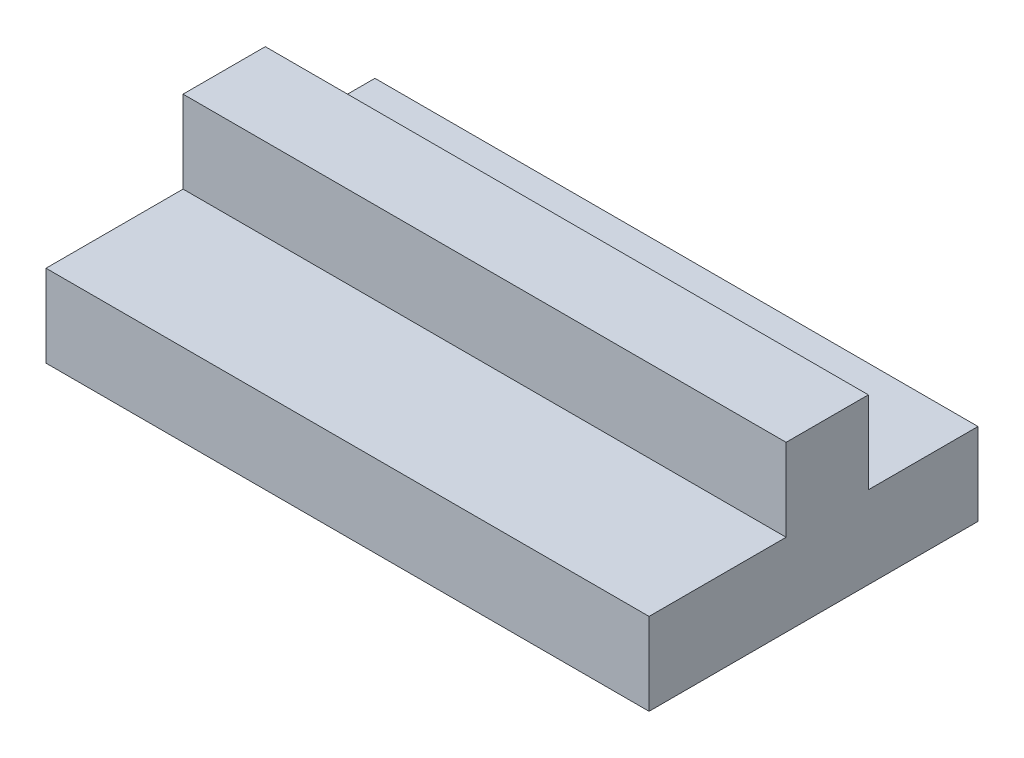
SolidWorks part; units mm, degrees
material "PET"
ref_plane "Спереди" through (0, 0, 0) normal (0, 0, 1) x (1, 0, 0)
ref_plane "Сверху" through (0, 0, 0) normal (0, 1, 0) x (1, 0, 0)
ref_plane "Справа" through (0, 0, 0) normal (1, 0, 0) x (0, 0, -1)
other "Configuration Table"
sketch "Основание & крышка" plane through (0, 0, 0) normal (0, 1, 0) x (1, 0, 0)
  line L1 (105, -26.5) -> (-105, -26.5)
  line L2 (105, -26.5) -> (105, 26.5)
  line L3 (105, 26.5) -> (-105, 26.5)
  line L4 (-105, -26.5) -> (-105, 26.5)
  line L5 (105, -26.5) -> (-105, 26.5) construction
  line L6 (105, 26.5) -> (-105, -26.5) construction
  line L7 (100, -21.5) -> (-100, -21.5)
  line L8 (100, -21.5) -> (100, 21.5)
  line L9 (100, 21.5) -> (-100, 21.5)
  line L10 (-100, -21.5) -> (-100, 21.5)
  line L11 (100, -21.5) -> (-100, 21.5) construction
  line L12 (100, 21.5) -> (-100, -21.5) construction
  point P0 (0, 0)
  point P5 (0, 0)
  dimension "D1" = 210
  dimension "D2" = 53
  dimension "D3" = 43
  dimension "D4" = 200
extrude "Бобышка-Вытянуть1" add sketch "Основание & крышка" along normal blind 50 contours L3 L4 L1 L2
sketch "Эскиз3" plane through (0, 0, 0) normal (0, -1, 0) x (1, 0, 0)
  line L0 (105, 26.5) -> (-105, 26.5) construction
  line L1 (-100, -21.5) -> (100, -21.5)
  line L2 (-100, -21.5) -> (-100, 21.5)
  line L3 (-100, 21.5) -> (100, 21.5)
  line L4 (100, -21.5) -> (100, 21.5)
  line L5 (-100, -21.5) -> (100, 21.5) construction
  line L6 (-100, 21.5) -> (100, -21.5) construction
  line L7 (105, 26.5) -> (105, -26.5) construction
  point P0 (0, 0)
  dimension "D1" = 5
  dimension "D2" = 5
extrude "Вырез-Вытянуть1" cut sketch "Эскиз3" against normal blind 45
sketch "Эскиз4" plane through (0, 50, 0) normal (0, 1, 0) x (1, 0, 0)
  line L0 (0, 41.131) -> (0, -55.5904) construction
  line L1 (105, 26.5) -> (-105, 26.5) construction
  line L2 (105, -26.5) -> (105, 26.5) construction
  line L3 (-127.2033, 0) -> (126.8125, 0) construction
  circle A0 centre (98, 19.5) radius 3.5
  circle A1 centre (-98, 19.5) radius 3.5
  circle A2 centre (98, -19.5) radius 3.5
  circle A3 centre (-98, -19.5) radius 3.5
  dimension "D1" = 7
  dimension "D3" = 7
  dimension "D2" = 7
sketch "Эскиз6" plane through (0, 50, 0) normal (0, 1, 0) x (1, 0, 0)
  line L0 (-117.6289, 0) -> (122.9046, 0) construction
  line L1 (0, 47.7745) -> (0, -57.5444) construction
extrude "Бобышка-Вытянуть2" add sketch "Эскиз4" along normal blind 2 draft 1 contours A0
fillet "Скругление2" radius 0.5 1 edges at (98, 52, -16.0349)
extrude "Бобышка-Вытянуть3" add sketch "Эскиз4<5>" along normal blind 2 contours A2
sketch "Эскиз4<5>" plane through (0, 50, 0) normal (0, 1, 0) x (1, 0, 0) same geometry as "Эскиз4"
extrude "Бобышка-Вытянуть4" add sketch "Эскиз4<6>" along normal blind 2 contours A3
sketch "Эскиз4<6>" plane through (0, 50, 0) normal (0, 1, 0) x (1, 0, 0) same geometry as "Эскиз4"
extrude "Бобышка-Вытянуть5" add sketch "Эскиз4<7>" along normal blind 2 contours A1
sketch "Эскиз4<7>" plane through (0, 50, 0) normal (0, 1, 0) x (1, 0, 0) same geometry as "Эскиз4"
fillet "Скругление3" radius 0.5 1 edges at (-98, 52, 23)
fillet "Скругление4" radius 0.5 1 edges at (-98, 52, -23)
fillet "Скругление5" radius 0.5 1 edges at (98, 52, 16)
sketch "Эскиз7" plane through (0, 0, -26.5) normal (0, 0, -1) x (-1, 0, 0)
  line L0 (0, -32.9698) -> (0, 82.1336) construction
  line L1 (-136.416, 24.5819) -> (136.5704, 24.5819) construction
  circle A0 centre (0, 35.0819) radius 6
  point P7 (0, 24.5819)
  dimension "D1" = 12
  dimension "D2" = 10.5
extrude "Вырез-Вытянуть2" cut sketch "Эскиз7" against normal blind 14 draft 5 contours A0
fillet "Скругление6" radius 2 1 edges at (-6, 35.0819, -26.5)
sketch "Эскиз8" plane through (0, 0, -21.5) normal (0, 0, 1) x (1, 0, 0)
  circle A0 centre (0, 35.0819) radius 7
  dimension "D1" = 14
extrude "Бобышка-Вытянуть6" add sketch "Эскиз8" along normal blind 7 draft 5 contours A0
sketch "Эскиз9" plane through (0, 0, -14.5) normal (0, 0, 1) x (1, 0, 0)
  circle A0 centre (0, 35.0819) radius 5.15
  dimension "D1" = 10.3
extrude "Вырез-Вытянуть3" cut sketch "Эскиз9" against normal blind 7 draft 5 draft outward yes
sketch "Эскиз10" plane through (0, 0, 26.5) normal (0, 0, 1) x (1, 0, 0)
  line L0 (0, -14.7722) -> (0, 61.6389) construction
  line L1 (-118.5615, 25) -> (116.6086, 25) construction
  line L2 (-127.2033, 50) -> (126.8125, 50) construction
  line L3 (-64.7, 38.15) -> (-35.3, 38.15)
  line L4 (-64.7, 38.15) -> (-64.7, 11.85)
  line L5 (-64.7, 11.85) -> (-35.3, 11.85)
  line L6 (-35.3, 38.15) -> (-35.3, 11.85)
  line L7 (-64.7, 38.15) -> (-35.3, 11.85) construction
  line L8 (-64.7, 11.85) -> (-35.3, 38.15) construction
  point P5 (-50, 25)
  point P13 (0, 25)
  dimension "D1" = 29.4
  dimension "D2" = 26.3
  dimension "D3" = 50
  dimension "D4" = 25
extrude "Вырез-Вытянуть4" cut sketch "Эскиз10" against normal blind 5
sketch "Эскиз13" plane through (0, 0, 21.5) normal (0, 0, -1) x (-1, 0, 0)
  line L0 (100, 45) -> (100, 0) construction
  line L1 (30.4, 38.75) -> (69.6, 38.75)
  line L2 (30.4, 38.75) -> (30.4, 11.25)
  line L3 (30.4, 11.25) -> (69.6, 11.25)
  line L4 (69.6, 38.75) -> (69.6, 11.25)
  line L5 (30.4, 38.75) -> (69.6, 11.25) construction
  line L6 (30.4, 11.25) -> (69.6, 38.75) construction
  line L8 (-100, 45) -> (100, 45) construction
  point P0 (50, 25)
  dimension "D1" = 50
  dimension "D2" = 20
  dimension "D3" = 27.5
  dimension "D4" = 39.2
extrude "Вырез-Вытянуть5" cut sketch "Эскиз13" against normal blind 2
sketch "Эскиз14" plane through (0, 0, 26.5) normal (0, 0, 1) x (1, 0, 0)
  line L0 (0, 0) -> (0, 50) construction
  line L1 (105, 0) -> (-105, 0) construction
  line L2 (105, 50) -> (-105, 50) construction
  line L3 (-105, 25) -> (105, 25) construction
  line L4 (-105, 50) -> (-105, 0) construction
  line L5 (105, 50) -> (105, 0) construction
  line L6 (-79.5, 28.8) -> (-73.5, 28.8)
  line L7 (-79.5, 15.2) -> (-73.5, 15.2)
  line L8 (-79.5, 15.2) -> (-79.5, 21.2)
  line L9 (-79.5, 21.2) -> (-73.5, 21.2)
  line L10 (-73.5, 15.2) -> (-73.5, 21.2)
  line L11 (-79.5, 15.2) -> (-73.5, 21.2) construction
  line L12 (-79.5, 21.2) -> (-73.5, 15.2) construction
  line L13 (-79.5, 28.8) -> (-73.5, 34.8) construction
  line L14 (-79.5, 34.8) -> (-79.5, 28.8)
  line L15 (-79.5, 34.8) -> (-73.5, 28.8) construction
  line L16 (-73.5, 34.8) -> (-73.5, 28.8)
  line L17 (-79.5, 34.8) -> (-73.5, 34.8)
  point P12 (-76.5, 18.2)
  point P21 (-76.5, 31.8)
  dimension "D1" = 6
  dimension "D2" = 6
  dimension "D3" = 18.2
  dimension "D4" = 25.5
extrude "Вырез-Вытянуть6" cut sketch "Эскиз14" against normal blind 5
sketch "Эскиз16" plane through (0, 0, 21.5) normal (0, 0, -1) x (-1, 0, 0)
  line L0 (-100, 45) -> (100, 45) construction
  line L1 (73.4, 34.85) -> (79.5, 34.85)
  line L2 (73.4, 34.85) -> (73.4, 28.75)
  line L3 (73.4, 28.75) -> (79.5, 28.75)
  line L4 (79.5, 34.85) -> (79.5, 28.75)
  line L5 (73.4, 34.85) -> (79.5, 28.75) construction
  line L6 (73.4, 28.75) -> (79.5, 34.85) construction
  line L7 (100, 45) -> (100, 0) construction
  point P0 (76.45, 31.8)
  dimension "D1" = 6.1
  dimension "D2" = 6.1
  dimension "D3" = 13.2
  dimension "D4" = 20.5
fillet "Скругление7" radius 2 8 edges at (-105, 25, -26.5) (-105, 50, 0) (0, 50, -26.5) (105, 25, -26.5) (105, 50, 0) (105, 25, 26.5) (-105, 25, 26.5) (0, 50, 26.5)
sketch "Эскиз17" plane through (0, 0, 0) normal (0, -1, 0) x (1, 0, 0)
  line L4 (-105, 24.5) -> (-105, -24.5)
  line L5 (-103, -26.5) -> (103, -26.5)
  line L6 (105, -24.5) -> (105, 24.5)
  line L7 (103, 26.5) -> (-103, 26.5)
  line L8 (-105, 24.5) -> (-105, -24.5)
  line L9 (-103, -26.5) -> (103, -26.5)
  line L10 (105, -24.5) -> (105, 24.5)
  line L11 (103, 26.5) -> (-103, 26.5)
  arc A4 (-105, -24.5) -> (-103, -26.5) centre (-103, -24.5) ccw
  arc A5 (103, -26.5) -> (105, -24.5) centre (103, -24.5) ccw
  arc A6 (105, 24.5) -> (103, 26.5) centre (103, 24.5) ccw
  arc A7 (-103, 26.5) -> (-105, 24.5) centre (-103, 24.5) ccw
  arc A8 (-105, -24.5) -> (-103, -26.5) centre (-103, -24.5) ccw
  arc A9 (103, -26.5) -> (105, -24.5) centre (103, -24.5) ccw
  arc A10 (105, 24.5) -> (103, 26.5) centre (103, 24.5) ccw
  arc A11 (-103, 26.5) -> (-105, 24.5) centre (-103, 24.5) ccw
  dimension "D1" = 0
extrude "Бобышка-Вытянуть8" add sketch "Эскиз17" along normal blind 3 separate body
sketch "Эскиз18" plane through (0, 0, 0) normal (0, 1, 0) x (1, 0, 0)
  line L8 (-100, -21.5) -> (100, -21.5)
  line L28 (-100, -21.5) -> (100, -21.5)
  line L32 (100, -21.5) -> (100, 21.5)
  line L34 (100, -21.5) -> (100, 21.5)
  line L36 (100, 21.5) -> (-100, 21.5)
  line L37 (100, 21.5) -> (-100, 21.5)
  line L38 (-100, 21.5) -> (-100, -21.5)
  line L39 (-100, 21.5) -> (-100, -21.5)
  dimension "D1" = 5
extrude "Крышка" add sketch "Эскиз18" along normal blind 3 from surface thin contours L37 L39 L28 L34 starting at face at (0, 0, 0) thin type one direction reverse wall 3
sketch "Эскиз20" plane through (0, -3, 0) normal (0, -1, 0) x (1, 0, 0)
  line L0 (-105, 0) -> (105, 0) construction
  line L1 (-105, 24.5) -> (-105, -24.5) construction
  line L2 (105, -24.5) -> (105, 24.5) construction
  line L3 (0, 26.5) -> (0, -26.5) construction
  line L4 (103, 26.5) -> (-103, 26.5) construction
  line L5 (-103, -26.5) -> (103, -26.5) construction
sketch "Эскиз21" plane through (0, -3, 0) normal (0, -1, 0) x (1, 0, 0)
  line L0 (-66.7, -49.4791) -> (-66.7, 41.6381) construction
  line L1 (-33.4, -45.2678) -> (-33.4, 45.8494) construction
  line L2 (33.4, -44.7574) -> (33.4, 46.3598) construction
  line L3 (66.7, -45.7783) -> (66.7, 45.3389) construction
  line L4 (105, -24.5) -> (105, 24.5) construction
  line L5 (0, 26.5) -> (0, -26.5) construction
  line L6 (0, -41.131) -> (0, 55.5904) construction
  line L7 (10.5, 60.8548) -> (10.5, -34.3859) construction
  line L12 (103, 26.5) -> (-103, 26.5) construction
  line L13 (8.4, 15.8) -> (12.6, 15.8)
  line L26 (8.4, 15.8) -> (8.4, 18)
  line L27 (8.4, 18) -> (12.6, 18)
  line L28 (12.6, 15.8) -> (12.6, 18)
  line L45 (8.4, 15.8) -> (12.6, 18) construction
  line L46 (8.4, 18) -> (12.6, 15.8) construction
  line L63 (14.5, 51.6017) -> (14.5, -2.5243) construction
  line L64 (20.6, 18) -> (16.4, 15.8) construction
  line L77 (20.6, 15.8) -> (16.4, 18) construction
  line L78 (16.4, 15.8) -> (16.4, 18)
  line L79 (20.6, 18) -> (16.4, 18)
  line L80 (20.6, 15.8) -> (20.6, 18)
  line L81 (20.6, 15.8) -> (16.4, 15.8)
  line L198 (0, 55.5904) -> (0, -41.131) construction
  point P14 (10.5, 16.9)
  point P21 (10.5, 18)
  point P28 (18.5, 16.9)
  dimension "D1" = 38.3
  dimension "D2" = 33.3
  dimension "D3" = 33.4
  dimension "D4" = 33.4
  dimension "D5" = 33.3
  dimension "D6" = 10.5
  dimension "D7" = 4.2
  dimension "D8" = 2.2
  dimension "D9" = 2.2
  dimension "D10" = 4
  dimension "D11" = 8.5
delete or keep bodies "Тело-Удалить/Сохранить 1" type keep bodies bodies 126
extrude "Вырез-Вытянуть7" cut sketch "Эскиз21" against normal blind 3
sketch "Эскиз23" plane through (0, -3, 0) normal (0, -1, 0) x (1, 0, 0)
  line L0 (14.6, 29.3333) -> (14.6, 9.3333) construction
  line L1 (12.6, 15.8) -> (12.6, 18) construction
  line L2 (3.6, 26.5) -> (3.6, 14.5)
  line L3 (103, 26.5) -> (-103, 26.5) construction
  line L4 (25.6, 14.5) -> (25.6, 26.5)
  line L6 (3.6, 14.5) -> (25.6, 14.5)
  line L11 (-105, 24.5) -> (-105, -24.5)
  line L12 (-103, -26.5) -> (103, -26.5)
  line L13 (105, -24.5) -> (105, 24.5)
  line L14 (103, 26.5) -> (-103, 26.5)
  line L18 (25.6, 26.5) -> (3.6, 26.5)
  arc A4 (-103, 26.5) -> (-105, 24.5) centre (-103, 24.5) ccw
  arc A5 (-105, -24.5) -> (-103, -26.5) centre (-103, -24.5) ccw
  arc A6 (103, -26.5) -> (105, -24.5) centre (103, -24.5) ccw
  arc A7 (105, 24.5) -> (103, 26.5) centre (103, 24.5) ccw
  dimension "D1" = 2
  dimension "D2" = 11
  dimension "D3" = 11
  dimension "D4" = 12
  dimension "D5" = 0
extrude "Вырез-Вытянуть8" cut sketch "Эскиз23" against normal blind 6 flip side to cut
